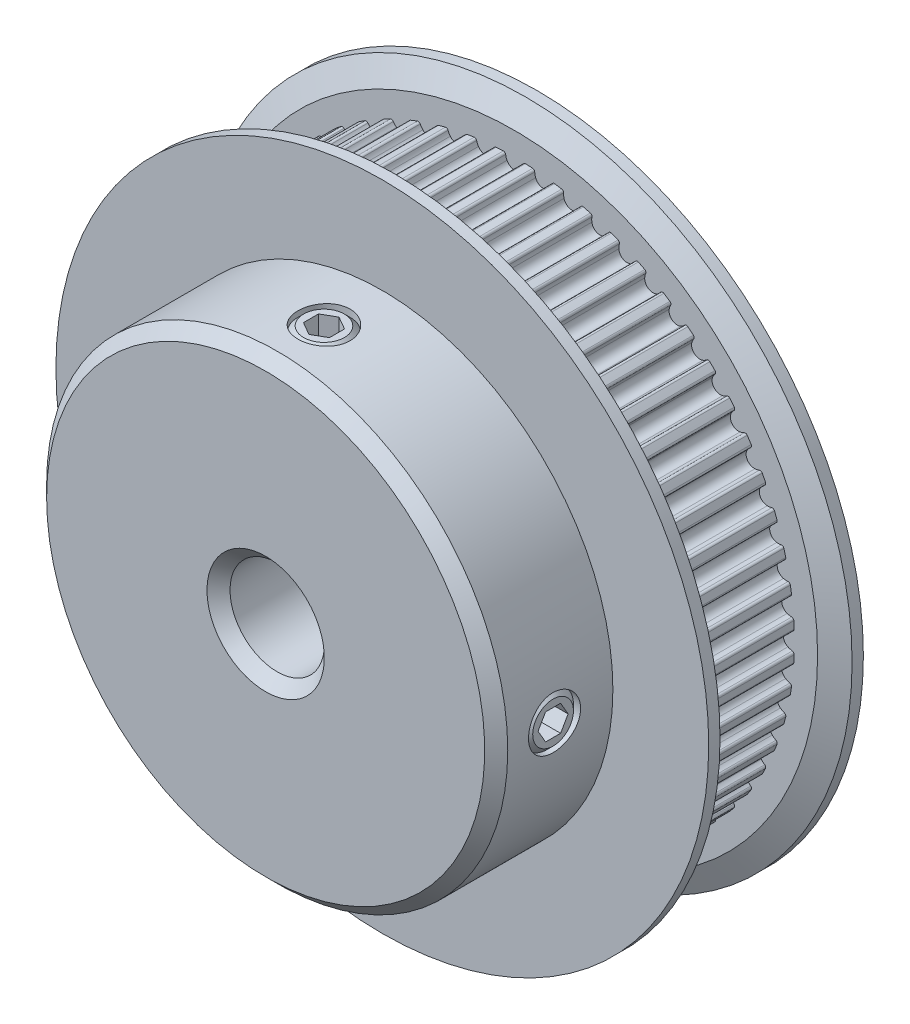
SolidWorks part; units mm, degrees
ref_plane "Front Plane" through (0, 0, 0) normal (0, 0, 1) x (1, 0, 0)
ref_plane "Top Plane" through (0, 0, 0) normal (0, 1, 0) x (1, 0, 0)
ref_plane "Right Plane" through (0, 0, 0) normal (1, 0, 0) x (0, 0, -1)
sketch "Sketch1" plane through (0, 0, 0) normal (0, 0, 1) x (1, 0, 0)
  line L1 (-1.9027, 18.097) -> (1.9027, 18.097) construction
  line L4 (0, 0) -> (0, 18.097) construction
  line L5 (0, 18.097) -> (0, 19.7579) construction
  line L6 (0, 19.101) -> (1.9973, 18.9963) construction
  line L7 (1.9973, 18.9963) -> (2.8966, 18.9017) construction
  line L8 (1.9973, 18.9963) -> (1.9027, 18.097) construction
  line L9 (-1.9973, 18.9963) -> (-1.9027, 18.097) construction
  line L10 (-1.9707, 18.7437) -> (-2.31, 21.971)
  line L11 (-2.31, 21.971) -> (2.31, 21.971)
  line L12 (2.31, 21.971) -> (1.9707, 18.7437)
  circle A0 centre (0, 0) radius 19.101 construction
  circle A1 centre (0, 0) radius 21.971 construction
  circle A2 centre (0, 0) radius 18.847 construction
  arc A3 (-0.4989, 18.4088) -> (0.4989, 18.4088) centre (0, 18.652) ccw
  arc A4 (-0.4989, 18.4088) -> (-0.5897, 18.7039) centre (0.4, 18.847) cw
  arc A5 (-1.9707, 18.7437) -> (-0.7441, 18.8323) centre (0, 0) cw
  arc A6 (-0.5897, 18.7039) -> (-0.7441, 18.8323) centre (-0.7382, 18.6824) ccw
  arc A7 (1.9707, 18.7437) -> (0.7441, 18.8323) centre (0, 0) ccw
  arc A8 (0.5897, 18.7039) -> (0.7441, 18.8323) centre (0.7382, 18.6824) cw
  arc A9 (0.4989, 18.4088) -> (0.5897, 18.7039) centre (-0.4, 18.847) ccw
  point P6 (0, 20.9083)
  point P11 (0, 19.101)
  point P13 (0, 21.971)
  point P14 (0, 18.847)
  dimension "D1" = 1.1505
  dimension "D2" = 0.6569
sketch "Sketch2" plane through (0, 0, 0) normal (1, 0, 0) x (0, 0, -1)
  line L0 (-9.1313, 3.175) -> (9.1313, 3.175)
  line L1 (-9.1313, 3.175) -> (-9.1313, 15.52)
  line L2 (-9.1313, 15.52) -> (-1.2787, 15.52)
  line L3 (-1.2787, 15.52) -> (-1.2787, 21.971)
  line L4 (-1.2787, 21.971) -> (0.2413, 21.971) construction
  line L5 (0.2413, 21.971) -> (0.2413, 18.847) construction
  line L6 (0.2413, 18.847) -> (7.6113, 18.847)
  line L7 (7.6113, 18.847) -> (7.6113, 21.971) construction
  line L8 (7.6113, 21.971) -> (9.1313, 21.971) construction
  line L9 (9.1313, 21.971) -> (9.1313, 3.175)
  line L10 (-9.1313, 0) -> (9.1313, 0) construction
  line L11 (8.3713, 21.971) -> (7.6113, 20.409)
  line L12 (0.2413, 20.409) -> (-0.5187, 21.971)
  line L13 (-1.2787, 21.971) -> (-0.5187, 21.971)
  line L14 (0.2413, 20.409) -> (0.2413, 18.847)
  line L15 (7.6113, 18.847) -> (7.6113, 20.409)
  line L16 (8.3713, 21.971) -> (9.1313, 21.971)
  arc A0 (0.2413, 20.409) -> (-0.5187, 21.971) centre (-1.7439, 20.409) ccw construction
  arc A1 (7.6113, 20.409) -> (8.3713, 21.971) centre (9.5965, 20.409) cw construction
  point P12 (0.2413, 20.409)
  point P14 (-0.5187, 21.971)
  point P20 (7.6113, 20.409)
  point P21 (8.3713, 21.971)
  point P25 (7.6113, 0)
  point P26 (0.2413, 0)
revolve "Revolve1" add sketch "Sketch2" angle 360 mid plane about L10
sketch "Sketch3" plane through (0, 0, 0) normal (0, 0, 1) x (1, 0, 0)
  line L6 (2.31, 21.971) -> (-2.31, 21.971)
  line L7 (1.9707, 18.7437) -> (2.31, 21.971)
  line L8 (-2.31, 21.971) -> (-1.9707, 18.7437)
  line L9 (2.31, 21.971) -> (-2.31, 21.971)
  line L10 (1.9707, 18.7437) -> (2.31, 21.971)
  line L11 (-2.31, 21.971) -> (-1.9707, 18.7437)
  arc A8 (1.9707, 18.7437) -> (0.7441, 18.8323) centre (0, 0) ccw
  arc A9 (0.7441, 18.8323) -> (0.5897, 18.7039) centre (0.7382, 18.6824) ccw
  arc A10 (0.4989, 18.4088) -> (0.5897, 18.7039) centre (-0.4, 18.847) ccw
  arc A11 (-0.4989, 18.4088) -> (0.4989, 18.4088) centre (0, 18.652) ccw
  arc A12 (-0.5897, 18.7039) -> (-0.4989, 18.4088) centre (0.4, 18.847) ccw
  arc A13 (-0.5897, 18.7039) -> (-0.7441, 18.8323) centre (-0.7382, 18.6824) ccw
  arc A14 (-0.7441, 18.8323) -> (-1.9707, 18.7437) centre (0, 0) ccw
  arc A15 (1.9707, 18.7437) -> (0.7441, 18.8323) centre (0, 0) ccw
  arc A16 (0.7441, 18.8323) -> (0.5897, 18.7039) centre (0.7382, 18.6824) ccw
  arc A17 (0.4989, 18.4088) -> (0.5897, 18.7039) centre (-0.4, 18.847) ccw
  arc A18 (-0.4989, 18.4088) -> (0.4989, 18.4088) centre (0, 18.652) ccw
  arc A19 (-0.5897, 18.7039) -> (-0.4989, 18.4088) centre (0.4, 18.847) ccw
  arc A20 (-0.5897, 18.7039) -> (-0.7441, 18.8323) centre (-0.7382, 18.6824) ccw
  arc A21 (-0.7441, 18.8323) -> (-1.9707, 18.7437) centre (0, 0) ccw
  dimension "D1" = 0
extrude "Cut-Extrude1" cut sketch "Sketch3" against normal up to vertex (7.6113 mm away) from vertex up to point (0, 18.847, -7.6113) starting at point (0, 18.847, -0.2413)
pattern_circular "CirPattern1" count 60 over 360 about axis through (0, 0, 9.1313) along (0, 0, 1) of "Cut-Extrude1"
sketch "Sketch4" plane through (0, 0, 0) normal (1, 0, 0) x (0, -1, 0)
  line L0 (0, -1.2787) -> (0, -9.1313) construction
  line L1 (-15.52, -1.2787) -> (15.52, -1.2787) construction
  line L2 (-15.52, -9.1313) -> (15.52, -9.1313) construction
  circle A0 centre (0, -5.205) radius 1.7526
extrude "Cut-Extrude2" cut sketch "Sketch4" along normal through all
ref_plane "Plane1" through (0, 0, 5.205) normal (0, 0, 1) x (1, 0, 0)
sketch "Sketch5" plane through (0, 0, 5.205) normal (0, 0, 1) x (1, 0, 0)
  line L0 (0, 0.1664) -> (0, 15.52) construction
  line L1 (3.175, -1.3716) -> (3.175, 0)
  line L2 (3.556, -1.7526) -> (15.0397, -1.7526)
  line L3 (3.175, 0) -> (15.52, 0) construction
  line L4 (3.175, 0) -> (15.4207, 0)
  line L5 (15.4207, 0) -> (15.4207, -1.3716)
  line L6 (3.556, -1.7526) -> (3.175, -1.3716)
  line L7 (15.4207, -1.3716) -> (15.0397, -1.7526)
  circle A0 centre (0, 0) radius 15.52 construction
  circle A1 centre (0, 0) radius 3.175 construction
  point P2 (3.175, -1.7526)
  point P11 (15.4207, -1.7526)
revolve "Revolve2" add sketch "Sketch5" angle 360 mid plane about L4
sketch "Sketch6" plane through (15.4207, 5.3841, 0) normal (-1, 0, 0) x (0, -1, 0)
  line L1 (5.3841, 6.2169) -> (4.5078, 5.7109)
  line L2 (4.5078, 5.7109) -> (4.5078, 4.6991)
  line L3 (4.5078, 4.6991) -> (5.3841, 4.1931)
  line L4 (5.3841, 4.1931) -> (6.2604, 4.6991)
  line L5 (6.2604, 4.6991) -> (6.2604, 5.7109)
  line L6 (6.2604, 5.7109) -> (5.3841, 6.2169)
  circle A0 centre (5.3841, 5.205) radius 0.8763 construction
  dimension "D1" = 1.7526
extrude "Cut-Extrude3" cut sketch "Sketch6" along normal blind 1.3144
pattern_circular "CirPattern2" count 2 over 90 about axis through (0, 0, 9.1313) along (0, 0, 1) of "Cut-Extrude2", "Revolve2", "Cut-Extrude3"
chamfer "Chamfer1" distance 0.776 angle 45 2 edges at (3.175, 0, 9.1313) (15.52, 0, 9.1313)
ref_axis "Center Axis 1" through (0, 0, -9.1313) along (0, 0, 1)
ref_plane "Contact Plane 1" through (0, 0, 9.1313) normal (0, 0, 1) x (1, 0, 0)
ref_plane "Contact Plane 2" through (0, 0, -9.1313) normal (0, 0, -1) x (-1, 0, 0)
equation "\"D2@Sketch1\" = \"D1@Sketch1\"/2"
equation "\"D1@Sketch6\" = \"Set Screw@Sketch4\" / 2"
equation "\"D1@Cut-Extrude3\" = \"D1@Sketch6\"*.75"
equation "\"D1@Chamfer1\"=\"Hub Dia@Sketch2\"*.025"
